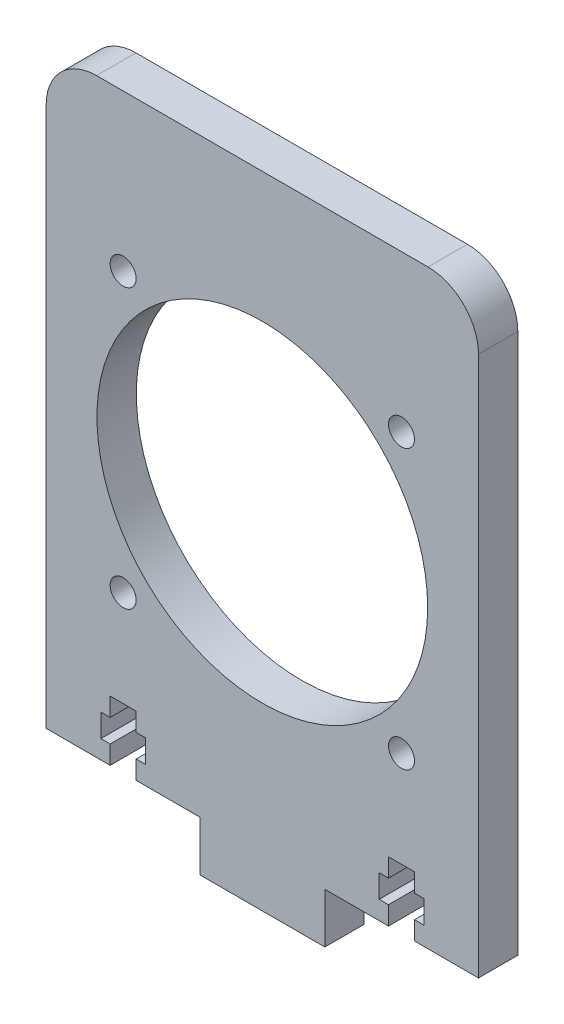
SolidWorks part; units mm, degrees
ref_plane "Front Plane" through (0, 0, 0) normal (0, 0, 1) x (1, 0, 0)
ref_plane "Top Plane" through (0, 0, 0) normal (0, 1, 0) x (1, 0, 0)
ref_plane "Right Plane" through (0, 0, 0) normal (1, 0, 0) x (0, 0, -1)
sketch "Sketch1" plane through (0, 0, 0) normal (0, 0, 1) x (1, 0, 0)
  line L0 (0, 0) -> (-35.3553, 35.3553) construction
  line L1 (-54.9, 75) -> (54.9, 75)
  line L2 (-54.9, 75) -> (-54.9, -75)
  line L3 (-54.9, -75) -> (54.9, -75)
  line L4 (54.9, 75) -> (54.9, -75)
  line L7 (-54.9, 0) -> (54.9, 0) construction
  line L8 (0, 75) -> (0, -75) construction
  circle A0 centre (0, 0) radius 42
  circle A1 centre (-35.3553, 35.3553) radius 3.3
  circle A2 centre (35.3553, 35.3553) radius 3.3
  circle A3 centre (35.3553, -35.3553) radius 3.3
  circle A4 centre (-35.3553, -35.3553) radius 3.3
  dimension "D1" = 84
  dimension "D5" = 6.6
  dimension "D2" = 109.8
  dimension "D3" = 150
  dimension "D4" = 45
  dimension "D6" = 50
extrude "Boss-Extrude1" add sketch "Sketch1" along normal blind 10 contours L4 L1 L2 L3 A2 A1 A0 A3 A4 region at (0, 73.1411, 0)
sketch "Sketch2" plane through (0, 0, 0) normal (0, 0, -1) x (-1, 0, 0)
  line L0 (0, -75) -> (32.05, -75)
  line L1 (54.9, -75) -> (-54.9, -75) construction
  line L2 (32.05, -75) -> (32.05, -70.3)
  line L3 (32.05, -70.3) -> (29.686, -70.3)
  line L4 (29.686, -70.3) -> (29.686, -64.46)
  line L5 (29.686, -64.46) -> (32.05, -64.46)
  line L6 (32.05, -64.46) -> (32.05, -59.76)
  line L7 (32.05, -59.76) -> (38.65, -59.76)
  line L8 (38.65, -59.76) -> (38.65, -64.46)
  line L9 (38.65, -64.46) -> (41.014, -64.46)
  line L10 (41.014, -64.46) -> (41.014, -70.3)
  line L11 (41.014, -70.3) -> (38.65, -70.3)
  line L12 (38.65, -70.3) -> (38.65, -75)
  line L13 (38.65, -75) -> (32.05, -75)
  line L14 (0, -75) -> (0, 0) construction
  line L15 (-38.65, -75) -> (-32.05, -75)
  line L16 (-38.65, -70.3) -> (-38.65, -75)
  line L17 (-41.014, -70.3) -> (-38.65, -70.3)
  line L18 (-41.014, -64.46) -> (-41.014, -70.3)
  line L19 (-38.65, -64.46) -> (-41.014, -64.46)
  line L20 (-38.65, -59.76) -> (-38.65, -64.46)
  line L21 (-32.05, -59.76) -> (-38.65, -59.76)
  line L22 (-32.05, -64.46) -> (-32.05, -59.76)
  line L23 (-29.686, -64.46) -> (-32.05, -64.46)
  line L24 (-29.686, -70.3) -> (-29.686, -64.46)
  line L25 (-32.05, -70.3) -> (-29.686, -70.3)
  line L26 (-32.05, -75) -> (-32.05, -70.3)
  line M18 (-54.9, -75) -> (54.9, -75)
  dimension "D1" = 32.05
  dimension "D2" = 5.84
  dimension "D3" = 6.6
  dimension "D4" = 15.24
  dimension "D5" = 11.328
extrude "Cut-Extrude1" cut sketch "Sketch2" against normal through all contours L26 L25 L24 L23 L22 L21 L20 L19 L18 L17 L16 M18 | L2 L3 L4 L5 L6 L7 L8 L9 L10 L11 L12 L13 region at (35.35, -67.38, 0)
sketch "Sketch4" plane through (0, -75, 0) normal (0, -1, 0) x (1, 0, 0)
  line L0 (0, 0) -> (15.875, 0)
  line L1 (-32.05, 0) -> (32.05, 0) construction
  line L2 (15.875, 0) -> (15.875, 10)
  line L3 (-32.05, 10) -> (32.05, 10) construction
  line L4 (15.875, 10) -> (-15.875, 10)
  line L5 (-15.875, 10) -> (-15.875, 0)
  line L6 (-15.875, 0) -> (0, 0)
  dimension "D1" = 31.75
extrude "Boss-Extrude2" add sketch "Sketch4" along normal blind 12.7
fillet "Fillet1" radius 12.8 2 edges at (-54.9, 75, 5) (54.9, 75, 5)
